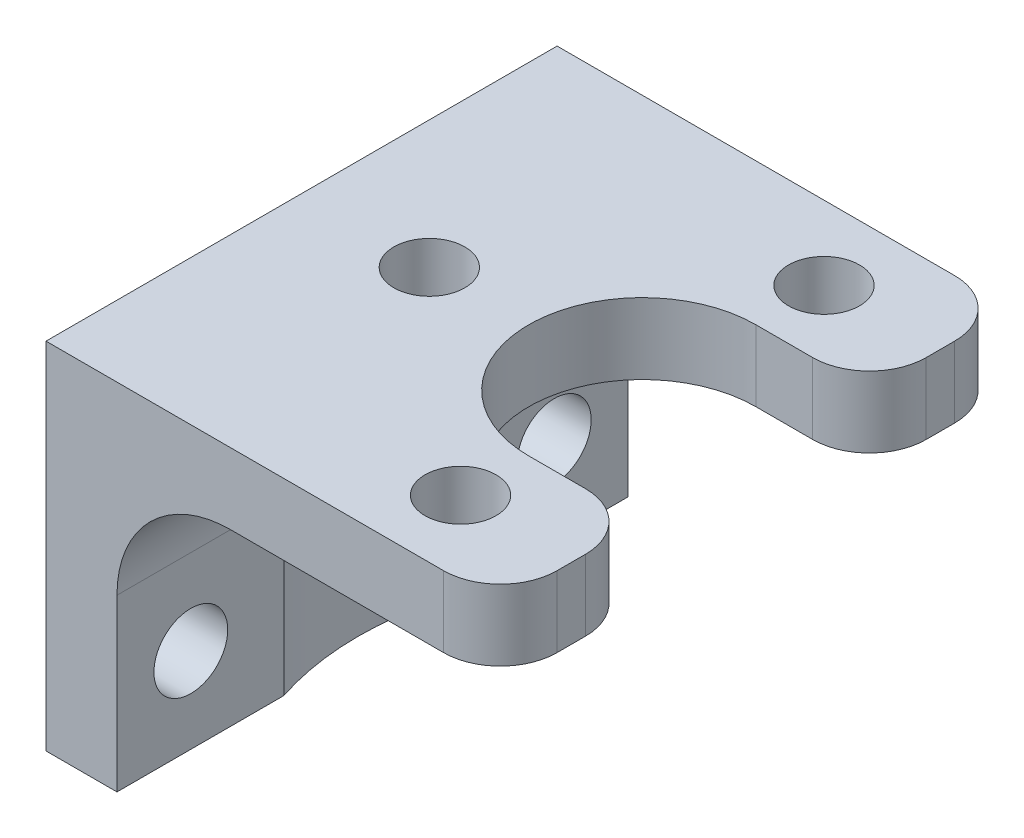
SolidWorks part; units mm, degrees
ref_plane "Front Plane" through (0, 0, 0) normal (0, 0, 1) x (1, 0, 0)
ref_plane "Top Plane" through (0, 0, 0) normal (0, 1, 0) x (1, 0, 0)
ref_plane "Right Plane" through (0, 0, 0) normal (1, 0, 0) x (0, 0, -1)
sketch "Sketch1" plane through (0, 0, 0) normal (0, 1, 0) x (1, 0, 0)
  line L1 (-10.16, -11.43) -> (10.16, -11.43)
  line L2 (-10.16, -11.43) -> (-10.16, 11.43)
  line L3 (-10.16, 11.43) -> (10.16, 11.43)
  line L4 (10.16, -11.43) -> (10.16, 11.43)
  line L5 (-10.16, -11.43) -> (10.16, 11.43) construction
  line L6 (-10.16, 11.43) -> (10.16, -11.43) construction
  point P0 (0, 0)
  dimension "D1" = 20.32
  dimension "D2" = 22.86
extrude "Boss-Extrude1" add sketch "Sketch1" along normal blind 3.175
fillet "Fillet1" radius 2.54 1 edges at (10.16, 1.5875, -11.43) type face fillet first side face at (10.16, 1.5875, 0) second side face at (0, 1.5875, -11.43)
fillet "Fillet2" radius 2.54 1 edges at (10.16, 1.5875, 11.43) type face fillet first side face at (10.16, 1.5875, 1.27) second side face at (0, 1.5875, 11.43)
sketch "Sketch2" plane through (0, 0, 0) normal (0, -1, 0) x (1, 0, 0)
  line L0 (-10.16, -11.43) -> (-10.16, 11.43) construction
  line L1 (7.62, -11.43) -> (-10.16, -11.43) construction
  line L2 (5.08, -5.08) -> (10.16, -5.08)
  line L3 (10.16, 8.89) -> (10.16, -8.89) construction
  line L4 (5.08, 5.08) -> (10.16, 5.08)
  line L5 (10.16, 5.08) -> (10.16, -5.08)
  arc A0 (5.08, 5.08) -> (5.08, -5.08) centre (5.08, 0) ccw
  dimension "D1" = 10.16
  dimension "D2" = 15.24
  dimension "D3" = 11.43
  dimension "D4" = 5.08
extrude "Cut-Extrude2" cut sketch "Sketch2" against normal through all
fillet "Fillet3" radius 2.54 1 edges at (10.16, 1.5875, 5.08) type face fillet first side face at (10.16, 1.5875, 6.985) second side face at (7.62, 1.5875, 5.08)
fillet "Fillet4" radius 2.54 1 edges at (10.16, 1.5875, -5.08) type face fillet first side face at (10.16, 1.5875, -6.985) second side face at (7.62, 1.5875, -5.08)
sketch "Sketch4" plane through (0, 0, 0) normal (0, -1, 0) x (1, 0, 0)
  line L0 (7.62, -11.43) -> (-10.16, -11.43) construction
  line L1 (-10.16, 11.43) -> (-6.985, 11.43)
  line L2 (-10.16, 11.43) -> (-10.16, -11.43)
  line L3 (-10.16, -11.43) -> (-6.985, -11.43)
  line L4 (-6.985, 11.43) -> (-6.985, -11.43)
  dimension "D1" = 3.175
extrude "Boss-Extrude2" add sketch "Sketch4" along normal blind 12.7
fillet "Fillet6" radius 5.08 1 edges type face fillet first side face at (5.3612, 0, -0.9525) second side face at (-6.985, -9.525, -2.8575)
sketch "Sketch3" plane through (0, 0, 0) normal (0, -1, 0) x (1, 0, 0)
  line L0 (7.62, -11.43) -> (-1.905, -11.43) construction
  line L1 (-1.905, 11.43) -> (7.62, 11.43) construction
  line L2 (-10.16, -11.43) -> (-10.16, 11.43) construction
  circle A0 centre (5.08, 8.128) radius 1.5875
  circle A1 centre (5.08, -8.128) radius 1.5875
  circle A2 centre (-4.445, 0) radius 1.5875
  dimension "D1" = 16.256
  dimension "D4" = 3.175
  dimension "D5" = 3.175
  dimension "D7" = 3.175
  dimension "D2" = 3.302
  dimension "D3" = 3.302
  dimension "D6" = 15.24
  dimension "D8" = 9.525
  dimension "D9" = 11.43
extrude "Cut-Extrude3" cut sketch "Sketch3" against normal mid plane 12.7
sketch "Sketch5" plane through (0, 0, 0) normal (0, -1, 0) x (1, 0, 0)
  line L0 (-10.16, 11.43) -> (-10.16, -11.43) construction
  line L1 (7.62, -11.43) -> (-1.905, -11.43) construction
  circle A0 centre (5.08, 0) radius 12.7
  dimension "D1" = 25.4
  dimension "D2" = 15.24
  dimension "D3" = 11.43
extrude "Cut-Extrude4" cut sketch "Sketch5" along normal through all
sketch "Sketch6" plane through (-6.985, 0, 0) normal (1, 0, 0) x (0, 0, -1)
  line L0 (11.43, -12.7) -> (11.43, -5.08) construction
  line L1 (-11.43, -12.7) -> (-11.43, -5.08) construction
  line L2 (11.43, -12.7) -> (3.9656, -12.7) construction
  circle A0 centre (-8.128, -8.89) radius 1.651
  circle A1 centre (8.128, -8.89) radius 1.651
  point P6 (-11.43, -8.89)
  dimension "D1" = 3.302
  dimension "D2" = 3.302
  dimension "D3" = 16.256
  dimension "D4" = 3.302
  dimension "D5" = 3.302
  dimension ".2" = 3.81
extrude "Cut-Extrude5" cut sketch "Sketch6" against normal through all
